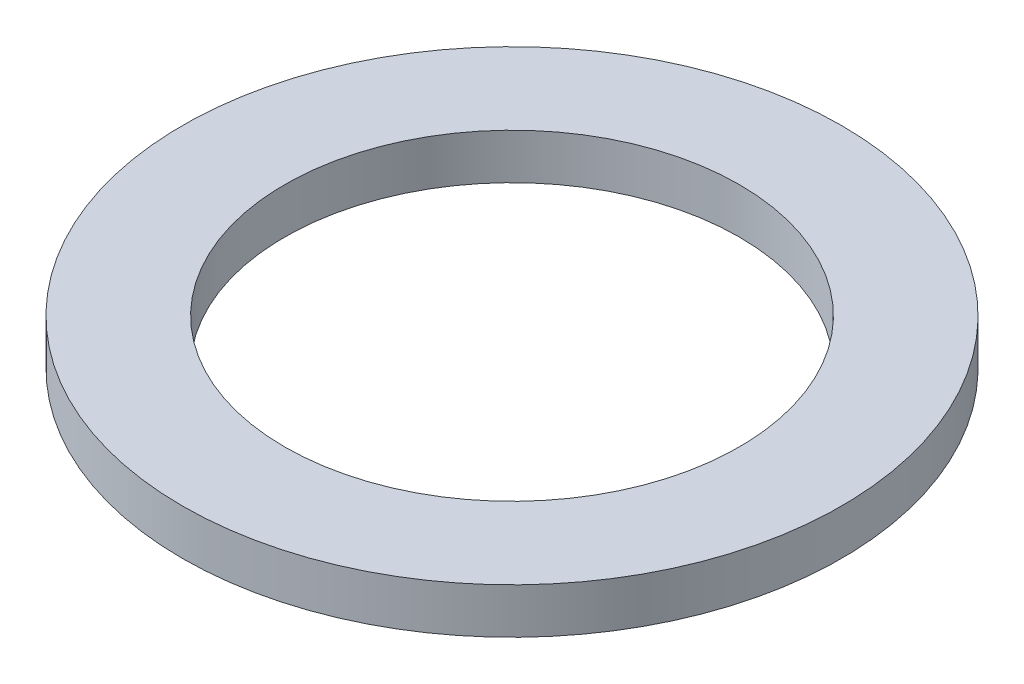
SolidWorks part; units mm, degrees
ref_plane "Front Plane" through (0, 0, 0) normal (0, 0, 1) x (1, 0, 0)
ref_plane "Top Plane" through (0, 0, 0) normal (0, 1, 0) x (1, 0, 0)
ref_plane "Right Plane" through (0, 0, 0) normal (1, 0, 0) x (0, 0, -1)
sketch "Sketch1" plane through (0, 0, 0) normal (0, 1, 0) x (1, 0, 0)
  circle A0 centre (0, 0) radius 72.5
  dimension "FLANGE_OD" = 145
extrude "Boss-Extrude1" add sketch "Sketch1" along normal blind 10
sketch "Sketch2" plane through (0, 0, 0) normal (0, 1, 0) x (1, 0, 0)
  circle A0 centre (0, 0) radius 50
  dimension "BORE_D" = 100
extrude "Cut-Extrude1" cut sketch "Sketch2" along normal through all
sketch "Sketch3" plane through (0, 10, 0) normal (0, 1, 0) x (1, 0, 0)
  circle A0 centre (0, 0) radius 26.8512 construction
  circle A1 centre (-26.8512, 0) radius 2.1094
  dimension "BOLT_D" = 4.2188
  dimension "BOLT_PCD" = 53.7023
extrude "Cut-Extrude2" cut sketch "Sketch3" against normal blind 8.5085 rebuild error yes
pattern_circular "CirPattern1" count 5 over 360 rebuild error yes
